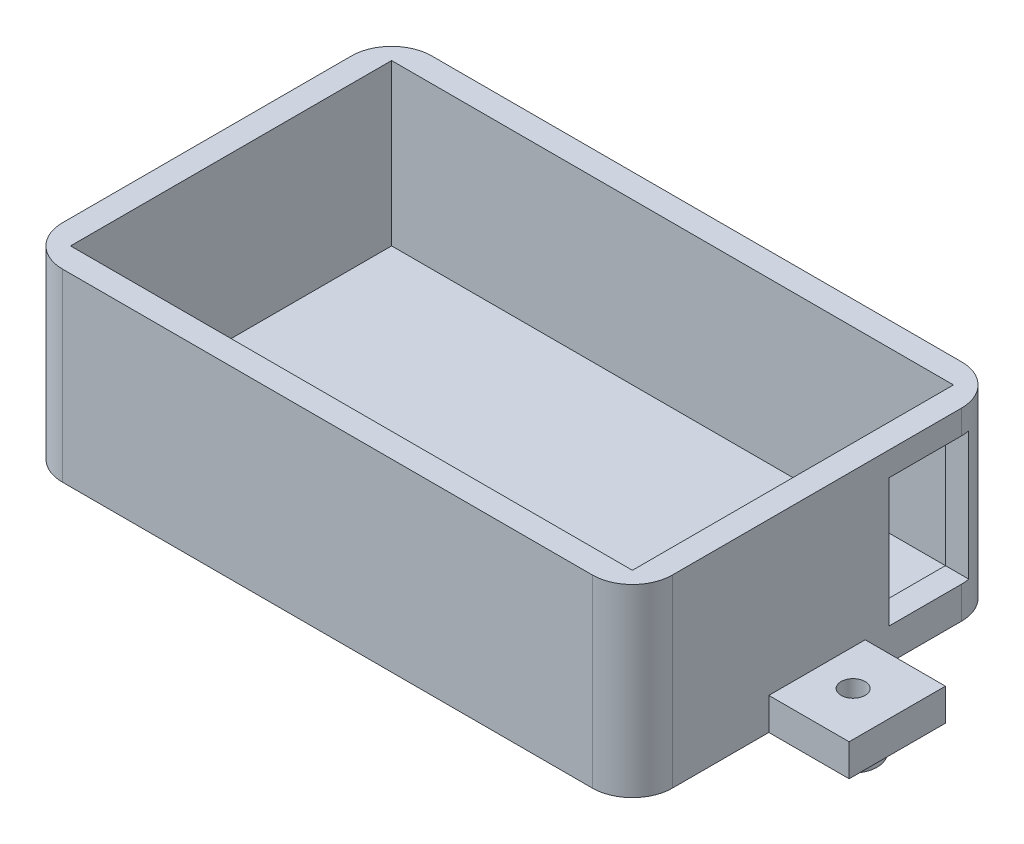
SolidWorks part; units mm, degrees
ref_plane "Alzado" through (0, 0, 0) normal (0, 0, 1) x (1, 0, 0)
ref_plane "Planta" through (0, 0, 0) normal (0, 1, 0) x (1, 0, 0)
ref_plane "Vista lateral" through (0, 0, 0) normal (1, 0, 0) x (0, 0, -1)
sketch "Croquis1" plane through (0, 0, 0) normal (0, 1, 0) x (1, 0, 0)
  line L1 (-35, 20) -> (35, 20)
  line L2 (-35, 20) -> (-35, -20)
  line L3 (-35, -20) -> (35, -20)
  line L4 (35, 20) -> (35, -20)
  line L5 (-35, 20) -> (35, -20) construction
  line L6 (-35, -20) -> (35, 20) construction
  line L7 (-38, -23) -> (38, -23)
  line L8 (-38, -23) -> (-38, 23)
  line L9 (-38, 23) -> (38, 23)
  line L10 (38, -23) -> (38, 23)
  line L11 (-38, -23) -> (38, 23) construction
  line L12 (-38, 23) -> (38, -23) construction
  point P0 (0, 0)
  point P6 (0, 0)
  dimension "D1" = 70
  dimension "D2" = 40
  dimension "D3" = 76
  dimension "D4" = 46
extrude "Saliente-Extruir1" add sketch "Croquis1" along normal blind 20
sketch "Croquis2" plane through (0, 0, 0) normal (0, -1, 0) x (1, 0, 0)
  line L1 (-38, 23) -> (38, 23)
  line L2 (-38, 23) -> (-38, -23)
  line L3 (-38, -23) -> (38, -23)
  line L4 (38, 23) -> (38, -23)
extrude "Saliente-Extruir2" add sketch "Croquis2" along normal blind 3
sketch "Croquis3" plane through (0, -3, 0) normal (0, -1, 0) x (1, 0, 0)
  line L0 (0, 0) -> (42.5, 0)
  line L1 (0, 0) -> (-42.5, 0)
  circle A0 centre (42.5, 0) radius 1.5
  circle A1 centre (42.5, 0) radius 3
  circle A2 centre (-42.5, 0) radius 1.5
  circle A3 centre (-42.5, 0) radius 3
  dimension "D2" = 3
  dimension "D3" = 6
  dimension "D5" = 3
  dimension "D6" = 6
  dimension "D1" = 42.5
  dimension "D4" = 42.5
extrude "Saliente-Extruir3" add sketch "Croquis3" along normal blind 3 and the other way blind 4 separate body contours A3 | A2 | A1 | A0
sketch "Croquis4" plane through (38, 0, 0) normal (1, 0, 0) x (0, 0, -1)
  line L0 (6, -3) -> (0, -3)
  line L1 (23, -3) -> (-23, -3) construction
  line L3 (6, -3) -> (-6, -3)
  line L4 (6, -3) -> (6, 1)
  line L5 (6, 1) -> (-6, 1)
  line L6 (-6, -3) -> (-6, 1)
  dimension "D1" = 6
  dimension "D2" = 12
  dimension "D3" = 4
extrude "Saliente-Extruir4" add sketch "Croquis4" along direction (-1, 0, 0) on the side of the normal blind 10 contours L4 L3 L6 L5
sketch "Croquis5" plane through (-38, 0, 0) normal (-1, 0, 0) x (0, 0, 1)
  line L0 (6, -3) -> (0, -3)
  line L1 (23, -3) -> (-23, -3) construction
  line L3 (6, -3) -> (-6, -3)
  line L4 (6, -3) -> (6, 1)
  line L5 (6, 1) -> (-6, 1)
  line L6 (-6, -3) -> (-6, 1)
  dimension "D1" = 6
  dimension "D2" = 4
  dimension "D3" = 12
extrude "Saliente-Extruir5" add sketch "Croquis5" along normal blind 10 contours L4 L3 L6 L5
sketch "Croquis6" plane through (0, -3, 0) normal (0, -1, 0) x (1, 0, 0)
  circle A0 centre (-42.5, 0) radius 1.5
  circle A1 centre (42.5, 0) radius 1.5
extrude "Cortar-Extruir1" cut sketch "Croquis6" against normal blind 10
sketch "Croquis7" plane through (38, 0, 0) normal (1, 0, 0) x (0, 0, -1)
  line L0 (23, 20) -> (19, 20)
  line L1 (-23, 20) -> (23, 20) construction
  line L2 (19, 20) -> (19, 17)
  line L4 (19, 17) -> (9, 17)
  line L5 (19, 17) -> (19, 1)
  line L6 (19, 1) -> (9, 1)
  line L7 (9, 17) -> (9, 1)
  point P9 (0, 0)
  dimension "D1" = 4
  dimension "D2" = 3
  dimension "D3" = 10
extrude "Cortar-Extruir2" cut sketch "Croquis7" against normal blind 10 contours L5 L4 L7 L6
fillet "Redondeo1" radius 5 4 edges at (-38, 8.5, 23) (-38, 8.5, -23) (38, 8.5, -23) (38, 8.5, 23)
